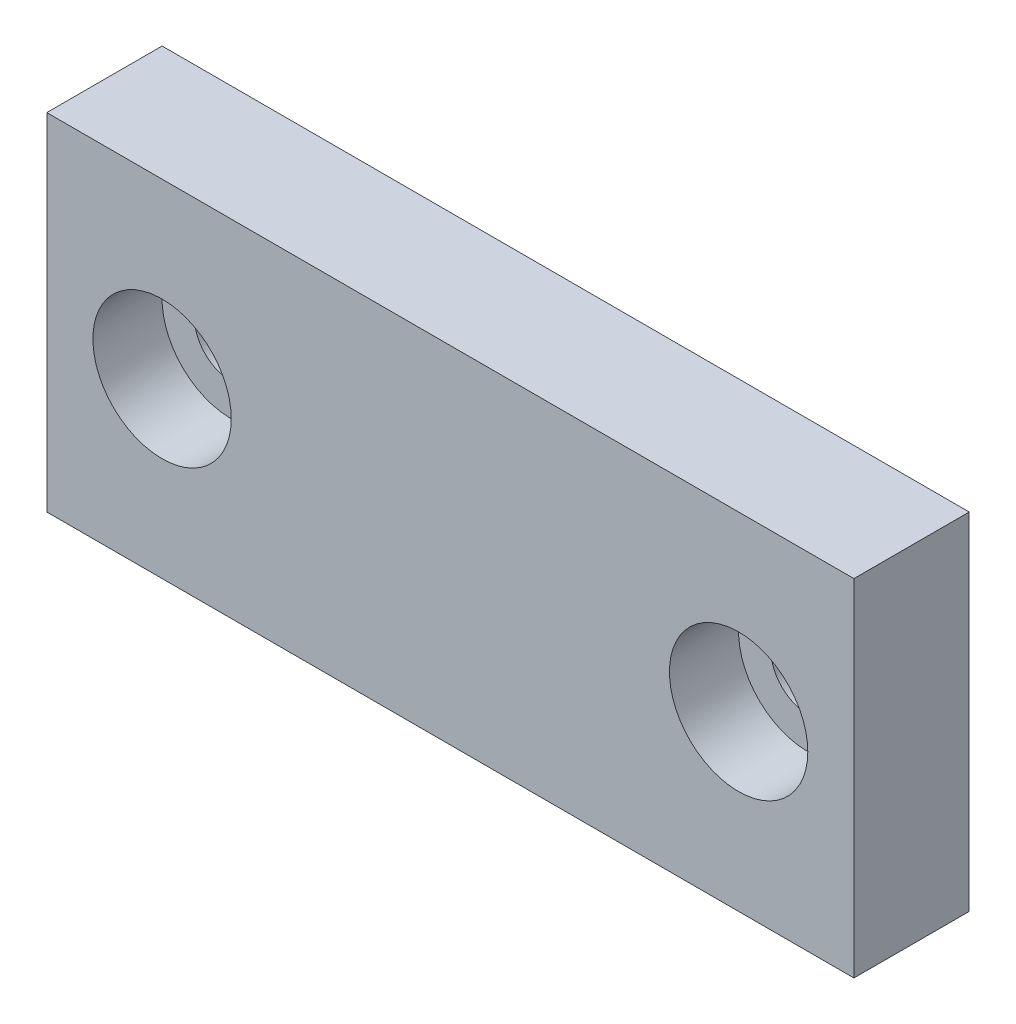
SolidWorks part; units mm, degrees
ref_plane "Front Plane" through (0, 0, 0) normal (0, 0, 1) x (1, 0, 0)
ref_plane "Top Plane" through (0, 0, 0) normal (0, 1, 0) x (1, 0, 0)
ref_plane "Right Plane" through (0, 0, 0) normal (1, 0, 0) x (0, 0, -1)
sketch "Sketch1" plane through (0, 0, 0) normal (0, 0, 1) x (1, 0, 0)
  line L0 (10, 0) -> (10, -30) construction
  line L1 (0, 0) -> (70, 0)
  line L2 (0, 0) -> (0, -30)
  line L3 (0, -30) -> (70, -30)
  line L4 (70, 0) -> (70, -30)
  line L5 (60, 0) -> (60, -30) construction
  dimension "D1" = 70
  dimension "D2" = 30
  dimension "D3" = 10
  dimension "D4" = 10
extrude "Boss-Extrude1" add sketch "Sketch1" along normal blind 10
sketch "Sketch2" plane through (0, 0, 10) normal (0, 0, 1) x (1, 0, 0)
  line L0 (60, 0) -> (60, -30) construction
  line L1 (10, 0) -> (10, -30) construction
  line L2 (60, 0) -> (60, -30)
  line L3 (10, 0) -> (10, -30)
  circle A0 centre (10, -15) radius 6
  circle A1 centre (60, -15) radius 6
  dimension "D1" = 12
  dimension "D2" = 12
extrude "Cut-Extrude1" cut sketch "Sketch2" against normal blind 6 contours A0 | A1
sketch "Sketch3" plane through (0, 0, 4) normal (0, 0, 1) x (1, 0, 0)
  line L0 (10, 0) -> (10, -30) construction
  line L1 (60, 0) -> (60, -30) construction
  circle A0 centre (10, -15) radius 3.2
  circle A1 centre (60, -15) radius 3.2
  dimension "D1" = 6.4
  dimension "D2" = 6.4
extrude "Cut-Extrude2" cut sketch "Sketch3" against normal through all
ref_plane "Plane1" through (0, 0, 0) normal (0, 1, 0) x (1, 0, 0)
sketch "Sketch9" plane through (0, 0, 0) normal (0, 1, 0) x (1, 0, 0)
  line L0 (50, -25.4) -> (50, -10)
  line L1 (70, -10) -> (0, -10) construction
  line L2 (20, -25.4) -> (20, -10)
  line L3 (20, -10) -> (50, -10)
  circle A0 centre (35, -25.4) radius 15
  arc A1 (20, -25.4) -> (50, -25.4) centre (35, -25.4) cw
  point P10 (0, 0)
  dimension "D1" = 30
sketch "Sketch10" plane through (0, 0, 10) normal (0, 0, 1) x (1, 0, 0)
  line L0 (10, -15) -> (60, -15) construction
  line L1 (10, 0) -> (10, -30) construction
  line L2 (60, 0) -> (60, -30) construction
